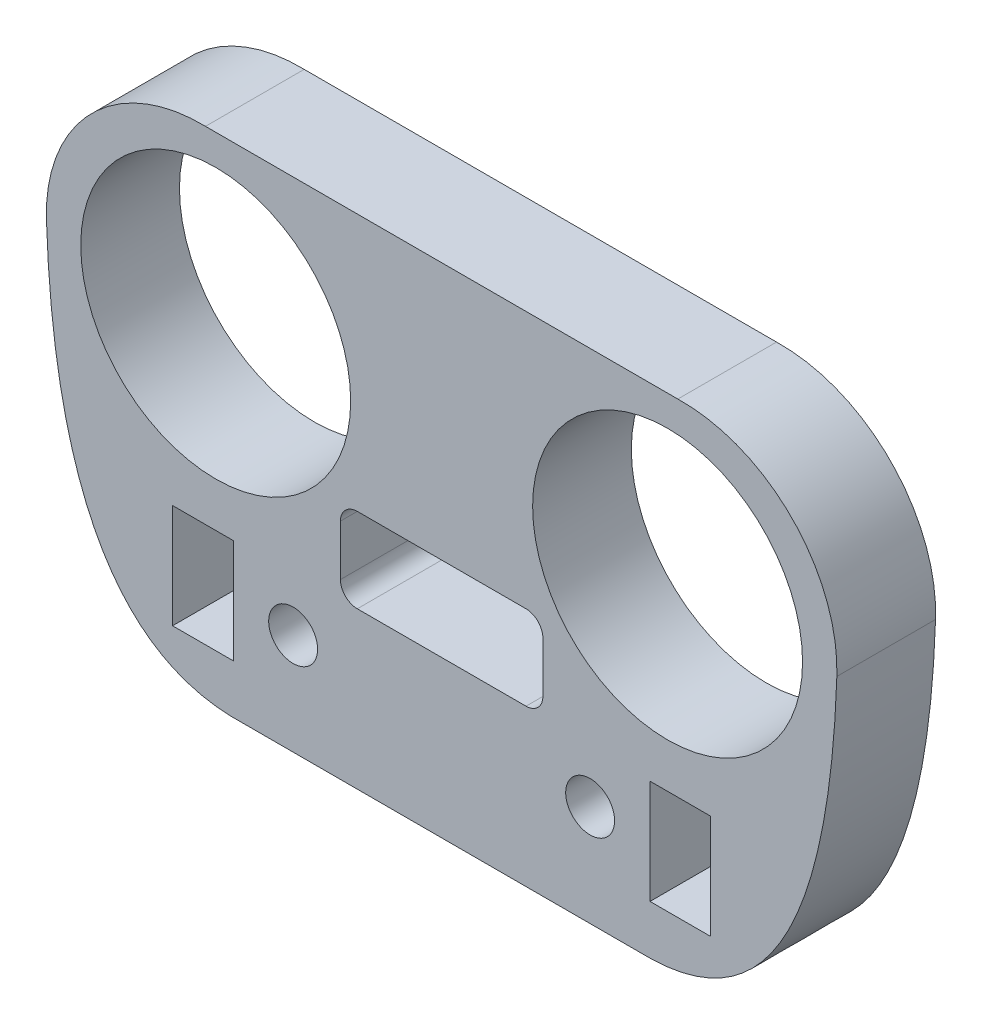
SolidWorks part; units mm, degrees
material "Acrylic (Medium-high impact)"
ref_plane "Front Plane" through (0, 0, 0) normal (0, 0, 1) x (1, 0, 0)
ref_plane "Top Plane" through (0, 0, 0) normal (0, 1, 0) x (1, 0, 0)
ref_plane "Right Plane" through (0, 0, 0) normal (1, 0, 0) x (0, 0, -1)
sketch "Model" plane through (0, 0, 0) normal (0, 0, 1) x (1, 0, 0)
  line L0 (549.6761, 574.3347) -> (554.6761, 574.3347)
  line L1 (554.6761, 576.8347) -> (548.6761, 576.8347) construction
  line L2 (554.6761, 576.8347) -> (560.6761, 576.8347) construction
  line L3 (554.6761, -405.4445) -> (554.6761, 49594.5555) construction
  line L4 (540.6774, 594.6) -> (568.6748, 594.6)
  line L5 (542.1922, 565.0732) -> (567.16, 565.0732)
  line L6 (549.6761, 579.3347) -> (554.6761, 579.3347)
  line L7 (567.0264, 574.1599) -> (567.0264, 567.9865)
  line L8 (570.6264, 574.1599) -> (567.0264, 574.1599)
  line L9 (570.6264, 567.9865) -> (570.6264, 574.1599)
  line L10 (567.0264, 567.9865) -> (570.6264, 567.9865)
  line L11 (560.6761, 578.3347) -> (560.6761, 575.3347)
  line L12 (559.6761, 579.3347) -> (554.6761, 579.3347)
  line L13 (559.6761, 574.3347) -> (554.6761, 574.3347)
  line L14 (538.7258, 571.0732) -> (570.6264, 571.0732) construction
  line L21 (548.6761, 578.3347) -> (548.6761, 575.3347)
  line L32 (542.3258, 567.9865) -> (538.7258, 567.9865)
  line L33 (538.7258, 567.9865) -> (538.7258, 574.1599)
  line L34 (538.7258, 574.1599) -> (542.3258, 574.1599)
  line L35 (542.3258, 574.1599) -> (542.3258, 567.9865)
  circle A0 centre (545.8738, 571.0732) radius 1.4498
  arc A1 (578.1008, 585.0732) -> (568.6748, 594.6) centre (568.8929, 585.3892) ccw
  circle A2 centre (541.284, 584.7975) radius 7.9999
  arc A3 (548.6761, 575.3347) -> (549.6761, 574.3347) centre (549.6761, 575.3347) ccw
  arc A4 (548.6761, 578.3347) -> (549.6761, 579.3347) centre (549.6761, 578.3347) cw
  arc A5 (560.6761, 578.3347) -> (559.6761, 579.3347) centre (559.6761, 578.3347) ccw
  arc A6 (560.6761, 575.3347) -> (559.6761, 574.3347) centre (559.6761, 575.3347) cw
  arc A7 (531.2514, 585.0732) -> (540.6774, 594.6) centre (540.4593, 585.3892) cw
  circle A8 centre (568.0682, 584.7975) radius 7.9999
  circle A9 centre (563.4784, 571.0732) radius 1.4498
  spline S0 degree 2 poles (578.1008, 585.0732) (577.4253, 565.393) (567.16, 565.0732) knots 0 0 0 1 1 1
  spline S48 degree 2 poles (531.2514, 585.0732) (531.9269, 565.393) (542.1922, 565.0732) knots 0 0 0 1 1 1
  point P2 (554.6761, 594.6)
  point P34 (554.6761, 565.0732)
  point P36 (554.6761, 576.8347)
  dimension "D1" = 3.548
  dimension "D2" = 8.8023
  dimension "D3" = 20
  dimension "D4" = 6.1735
  dimension "D5" = 12
  dimension "D6" = 5
  dimension "D7" = 3.6
  dimension "D8" = 29.5268
  dimension "D9" = 6
extrude "Boss-Extrude1" add sketch "Model" along normal blind 5.85 contours A7 S48 L5 S0 A1 L4 A9 L11 A6 L13 L0 A3 L21 A4 L6 L12 A5 A2 A0 L10 L7 L8 L9 L34 L35 L32 L33 A8 region at (554.6761, 594.0461, 0)
